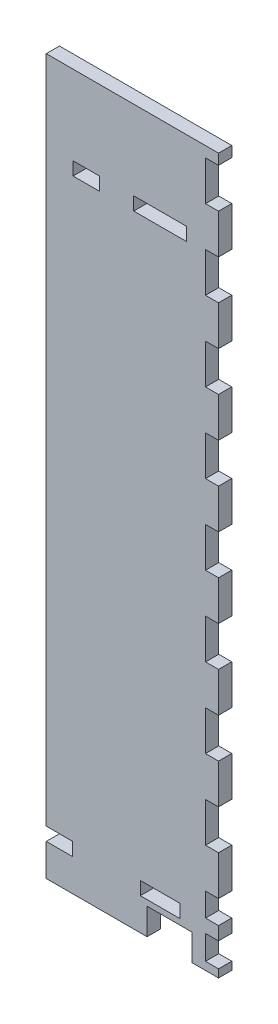
SolidWorks part; units mm, degrees
material "Balsa"
ref_plane "Plan de face" through (0, 0, 0) normal (0, 0, 1) x (1, 0, 0)
ref_plane "Plan de dessus" through (0, 0, 0) normal (0, 1, 0) x (1, 0, 0)
ref_plane "Plan de droite" through (0, 0, 0) normal (1, 0, 0) x (0, 0, -1)
sketch "Esquisse1" plane through (0, 0, 0) normal (0, 0, 1) x (1, 0, 0)
  line L1 (65.1211, 0) -> (0, 0)
  line L2 (65.1211, 0) -> (65.1211, 270)
  line L3 (65.1211, 270) -> (0, 270)
  line L4 (0, 0) -> (0, 270)
  dimension "D1" = 270
  dimension "D2" = 65.1211
extrude "Boss.-Extru.1" add sketch "Esquisse1" against normal blind 5
sketch "Esquisse2" plane through (0, 0, 0) normal (0, 0, 1) x (1, 0, 0)
  line L0 (0, 270) -> (0, 0) construction
  line L1 (0, 17.15) -> (10, 17.15)
  line L2 (0, 17.15) -> (0, 12.15)
  line L3 (0, 12.15) -> (10, 12.15)
  line L4 (10, 17.15) -> (10, 12.15)
  line L5 (65.1211, 0) -> (65.1211, 270) construction
  line L6 (50.5493, 17.15) -> (35.5493, 17.15)
  line L7 (50.5493, 17.15) -> (50.5493, 12.15)
  line L8 (50.5493, 12.15) -> (35.5493, 12.15)
  line L9 (35.5493, 17.15) -> (35.5493, 12.15)
  line L10 (65.1211, 12.15) -> (60.2011, 12.15)
  line L11 (65.1211, 12.15) -> (65.1211, 3)
  line L12 (65.1211, 3) -> (60.2011, 3)
  line L13 (60.2011, 12.15) -> (60.2011, 3)
  line L14 (0, 0) -> (65.1211, 0) construction
  line L15 (65.1211, 0) -> (65.1211, 270) construction
  line L16 (65.1211, 17.15) -> (60.2011, 17.15)
  line L17 (65.1211, 17.15) -> (65.1211, 26)
  line L18 (65.1211, 26) -> (60.2011, 26)
  line L19 (60.2011, 17.15) -> (60.2011, 26)
  line L20 (65.1211, 270) -> (0, 270) construction
  line L21 (65.1211, 266) -> (60.2011, 266)
  line L22 (65.1211, 266) -> (65.1211, 251)
  line L23 (65.1211, 251) -> (60.2011, 251)
  line L24 (60.2011, 266) -> (60.2011, 251)
  line L25 (65.1211, 236) -> (60.2011, 236)
  line L26 (65.1211, 236) -> (65.1211, 221)
  line L27 (65.1211, 221) -> (60.2011, 221)
  line L28 (60.2011, 236) -> (60.2011, 221)
  line L29 (65.1211, 206) -> (60.2011, 206)
  line L30 (65.1211, 206) -> (65.1211, 191)
  line L31 (65.1211, 191) -> (60.2011, 191)
  line L32 (60.2011, 206) -> (60.2011, 191)
  line L33 (65.1211, 176) -> (60.2011, 176)
  line L34 (65.1211, 176) -> (65.1211, 161)
  line L35 (65.1211, 161) -> (60.2011, 161)
  line L36 (60.2011, 176) -> (60.2011, 161)
  line L37 (65.1211, 146) -> (60.2011, 146)
  line L38 (65.1211, 146) -> (65.1211, 131)
  line L39 (65.1211, 131) -> (60.2011, 131)
  line L40 (60.2011, 146) -> (60.2011, 131)
  line L41 (65.1211, 116) -> (60.2011, 116)
  line L42 (65.1211, 116) -> (65.1211, 101)
  line L43 (65.1211, 101) -> (60.2011, 101)
  line L44 (60.2011, 116) -> (60.2011, 101)
  line L45 (65.1211, 86) -> (60.2011, 86)
  line L46 (65.1211, 86) -> (65.1211, 71)
  line L47 (65.1211, 71) -> (60.2011, 71)
  line L48 (60.2011, 86) -> (60.2011, 71)
  line L49 (65.1211, 56) -> (60.2011, 56)
  line L50 (65.1211, 56) -> (65.1211, 41)
  line L51 (65.1211, 41) -> (60.2011, 41)
  line L52 (60.2011, 56) -> (60.2011, 41)
  line L54 (10.1211, 240) -> (20.1211, 240)
  line L55 (10.1211, 240) -> (10.1211, 235)
  line L56 (10.1211, 235) -> (20.1211, 235)
  line L57 (20.1211, 240) -> (20.1211, 235)
  line L59 (33.0493, 235) -> (53.0493, 235)
  line L60 (33.0493, 235) -> (33.0493, 240)
  line L61 (33.0493, 240) -> (53.0493, 240)
  line L62 (53.0493, 235) -> (53.0493, 240)
  dimension "D1" = 3
  dimension "D2" = 4.92
  dimension "D3" = 9.15
  dimension "D4" = 12.15
  dimension "D5" = 5
  dimension "D6" = 5
  dimension "D7" = 15
  dimension "D8" = 5
  dimension "D9" = 15
  dimension "D10" = 4
  dimension "D12" = 30
  dimension "D13" = 10
  dimension "D14" = 20
  dimension "D15" = 55
  dimension "D16" = 5
  dimension "D17" = 12.0718
  dimension "D18" = 30
  dimension "D11" = 8
extrude "Enlèv. mat.-Extru.1" cut sketch "Esquisse2" against normal blind 5
sketch "Esquisse3" plane through (0, 0, 0) normal (0, 0, 1) x (1, 0, 0)
  line L0 (0, 0) -> (65.1211, 0) construction
  line L1 (38.1211, 0) -> (55.1211, 0)
  line L2 (38.1211, 0) -> (38.1211, 10)
  line L3 (38.1211, 10) -> (55.1211, 10)
  line L4 (55.1211, 0) -> (55.1211, 10)
  line L5 (65.1211, 0) -> (65.1211, 3) construction
  dimension "D1" = 10
  dimension "D2" = 10
  dimension "D3" = 17
extrude "Enlèv. mat.-Extru.2" cut sketch "Esquisse3" against normal blind 5
